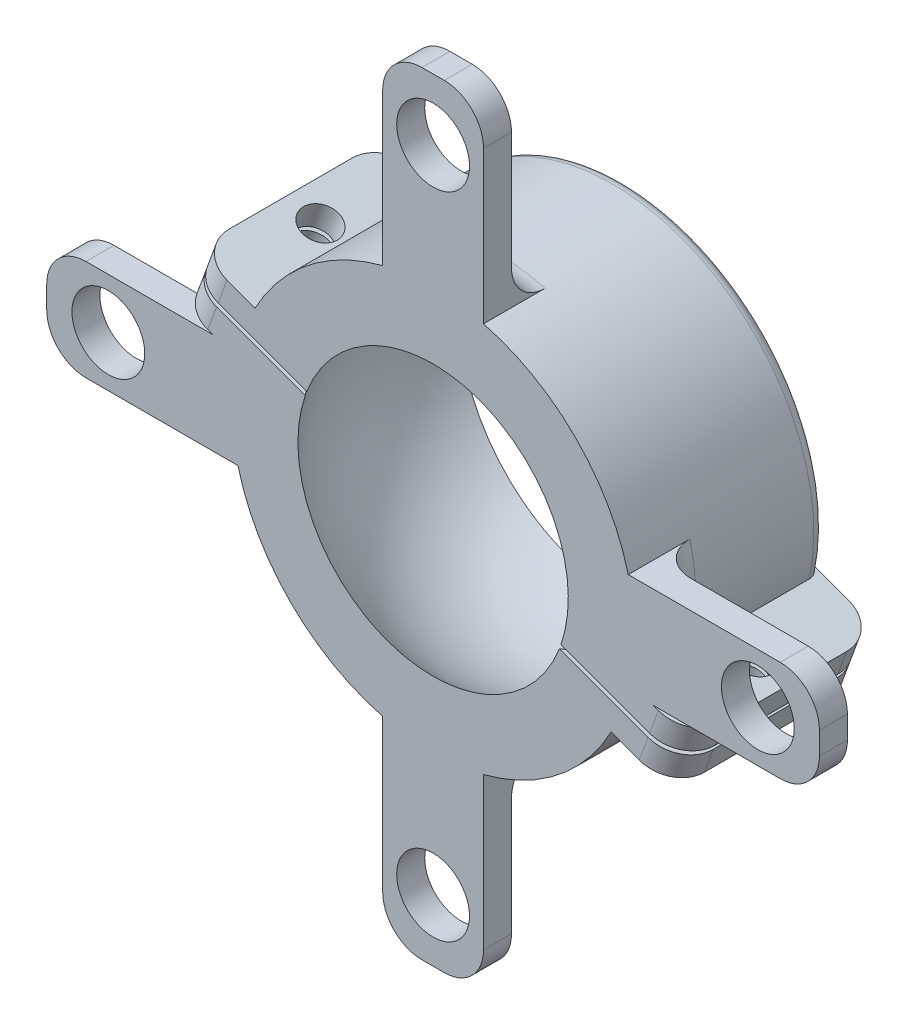
SolidWorks part; units mm, degrees
ref_plane "前视基准面" through (0, 0, 0) normal (0, 0, 1) x (1, 0, 0)
ref_plane "上视基准面" through (0, 0, 0) normal (0, 1, 0) x (1, 0, 0)
ref_plane "右视基准面" through (0, 0, 0) normal (1, 0, 0) x (0, 0, -1)
sketch "草图1" plane through (0, 0, 0) normal (0, 0, 1) x (1, 0, 0)
  circle A0 centre (0, 0) radius 18
extrude "凸台-拉伸1" add sketch "草图1" along normal blind 12.5 and the other way blind 6.5
sketch "草图2" plane through (0, 0, 0) normal (0, 0, 1) x (1, 0, 0)
  line L0 (0, 16) -> (0, -16)
  arc A0 (0, -16) -> (0, 16) centre (0, 0) ccw
revolve "切除-旋转1" cut sketch "草图2" angle 360 about L0
ref_plane "基准面1" through (17, 0, 0) normal (1, 0, 0) x (0, 0, -1)
ref_plane "基准面2" through (-17, 0, 0) normal (-1, 0, 0) x (0, 0, 1)
ref_plane "基准面3" through (0, 17, 0) normal (0, 1, 0) x (1, 0, 0)
ref_plane "基准面4" through (0, -17, 0) normal (0, -1, 0) x (-1, 0, 0)
sketch "草图4" plane through (17, 0, 0) normal (1, 0, 0) x (0, 0, -1)
  line L0 (-12.5, 18) -> (-12.5, -18) construction
  line L1 (-14.5, -4.5) -> (-10.5, -4.5)
  line L2 (-14.5, -4.5) -> (-14.5, 4.5)
  line L3 (-14.5, 4.5) -> (-10.5, 4.5)
  line L4 (-10.5, -4.5) -> (-10.5, 4.5)
  line L5 (-14.5, -4.5) -> (-10.5, 4.5) construction
  line L6 (-14.5, 4.5) -> (-10.5, -4.5) construction
  line L8 (-12.5, -4.5) -> (-10.5, -4.5)
  line L9 (-12.5, -4.5) -> (-12.5, 4.5)
  line L10 (-12.5, 4.5) -> (-10.5, 4.5)
  line L11 (-10.5, -4.5) -> (-10.5, 4.5)
  point P0 (-12.5, 0)
  dimension "D1" = 9
  dimension "D2" = 4
sketch "草图5" plane through (17, 0, 0) normal (1, 0, 0) x (0, 0, -1)
  line L1 (-10.5, 4.5) -> (-12.5, 4.5)
  line L2 (-10.5, 4.5) -> (-10.5, -4.5)
  line L3 (-10.5, -4.5) -> (-12.5, -4.5)
  line L4 (-12.5, 4.5) -> (-12.5, -4.5)
extrude "凸台-拉伸2" add sketch "草图5" along normal blind 17.5 and the other way blind 1
sketch "草图6" plane through (-17, 0, 0) normal (-1, 0, 0) x (0, 0, 1)
  line L1 (12.5, 4.5) -> (10.5, 4.5)
  line L2 (12.5, 4.5) -> (12.5, -4.5)
  line L3 (12.5, -4.5) -> (10.5, -4.5)
  line L4 (10.5, 4.5) -> (10.5, -4.5)
extrude "凸台-拉伸3" add sketch "草图6" along normal blind 17.5 and the other way blind 1
sketch "草图7" plane through (0, 17, 0) normal (0, 1, 0) x (1, 0, 0)
  line L0 (-17.4284, -12.5) -> (17.4284, -12.5) construction
  line L1 (-4.5, -14.5) -> (4.5, -14.5)
  line L2 (-4.5, -14.5) -> (-4.5, -10.5)
  line L3 (-4.5, -10.5) -> (4.5, -10.5)
  line L4 (4.5, -14.5) -> (4.5, -10.5)
  line L5 (-4.5, -14.5) -> (4.5, -10.5) construction
  line L6 (-4.5, -10.5) -> (4.5, -14.5) construction
  point P0 (0, -12.5)
  dimension "D1" = 4
  dimension "D2" = 9
sketch "草图8" plane through (0, 17, 0) normal (0, 1, 0) x (1, 0, 0)
  line L0 (-4.5, -14.5) -> (-4.5, -10.5) construction
  line L1 (4.5, -10.5) -> (-4.5, -10.5)
  line L2 (4.5, -10.5) -> (4.5, -12.5)
  line L3 (4.5, -12.5) -> (-4.5, -12.5)
  line L4 (-4.5, -10.5) -> (-4.5, -12.5)
extrude "凸台-拉伸4" add sketch "草图8" along normal blind 17.5 and the other way blind 1
sketch "草图9" plane through (0, -17, 0) normal (0, -1, 0) x (-1, 0, 0)
  line L1 (-4.5, -12.5) -> (4.5, -12.5)
  line L2 (-4.5, -12.5) -> (-4.5, -10.5)
  line L3 (-4.5, -10.5) -> (4.5, -10.5)
  line L4 (4.5, -12.5) -> (4.5, -10.5)
extrude "凸台-拉伸5" add sketch "草图9" along normal blind 17.5 and the other way blind 1
ref_axis "基准轴1" through (0, 0, -6.5) along (0, 0, 1)
ref_plane "基准面6" through (0, 0, 0) normal (0.342, 0.9397, 0) x (0, 0, 1)
ref_plane "基准面7" through (0, 0, 0) normal (-0.9397, 0.342, 0) x (0, 0, 1)
ref_plane "基准面8" through (-15.9748, 5.8143, 0) normal (-0.9397, 0.342, 0) x (0, 0, 1)
ref_plane "基准面9" through (15.9748, -5.8143, 0) normal (0.9397, -0.342, 0) x (0, 0, -1)
sketch "草图12" plane through (-15.9748, 5.8143, 0) normal (-0.9397, 0.342, 0) x (0, 0, 1)
  line L0 (12.5, -1.7323) -> (12.5, 14.8383) construction
  line L1 (-12.5, -2.5) -> (12.5, -2.5)
  line L2 (-12.5, -2.5) -> (-12.5, 2.5)
  line L3 (-12.5, 2.5) -> (12.5, 2.5)
  line L4 (12.5, -2.5) -> (12.5, 2.5)
  line L5 (-12.5, -2.5) -> (12.5, 2.5) construction
  line L6 (-12.5, 2.5) -> (12.5, -2.5) construction
  line L7 (12.5, -2.5) -> (-6.5, -2.5)
  point P0 (0, 0)
  dimension "D1" = 5
sketch "草图14" plane through (-15.9748, 5.8143, 0) normal (-0.9397, 0.342, 0) x (0, 0, 1)
  line L1 (-6.5, -2.5) -> (12.5, -2.5)
  line L2 (-6.5, -2.5) -> (-6.5, 2.5)
  line L3 (-6.5, 2.5) -> (12.5, 2.5)
  line L4 (12.5, -2.5) -> (12.5, 2.5)
extrude "凸台-拉伸6" add sketch "草图14" along normal blind 6.5
sketch "草图15" plane through (15.9748, -5.8143, 0) normal (0.9397, -0.342, 0) x (0, 0, -1)
  line L1 (-12.5, -2.5) -> (6.5, -2.5)
  line L2 (-12.5, -2.5) -> (-12.5, 2.5)
  line L3 (-12.5, 2.5) -> (6.5, 2.5)
  line L4 (6.5, -2.5) -> (6.5, 2.5)
extrude "凸台-拉伸7" add sketch "草图15" along normal blind 6.5
sketch "草图16" plane through (22.0828, -8.0375, 0) normal (0.9397, -0.342, 0) x (0, 0, -1)
  line L0 (-12.5, 2.5) -> (-12.5, 0.5)
  line L1 (-12.5, 2.5) -> (-12.5, -2.5) construction
  line L2 (6.5, -2.5) -> (6.5, -0.5)
  line L3 (6.5, -2.5) -> (6.5, 2.5) construction
  line L5 (-12.5, 0.5) -> (6.5, 0.5)
  line L6 (-12.5, 0.5) -> (-12.5, -0.5)
  line L7 (-12.5, -0.5) -> (6.5, -0.5)
  line L8 (6.5, 0.5) -> (6.5, -0.5)
  dimension "D1" = 1
sketch "草图17" plane through (22.0828, -8.0375, 0) normal (0.9397, -0.342, 0) x (0, 0, -1)
  line L0 (-12.5, 0.5) -> (-12.5, 0.2)
  line L5 (6.5, -0.5) -> (6.5, -0.2)
  line L7 (6.5, -0.2) -> (-12.5, -0.2)
  line L8 (6.5, -0.2) -> (6.5, 0.2)
  line L9 (6.5, 0.2) -> (-12.5, 0.2)
  line L10 (-12.5, -0.2) -> (-12.5, 0.2)
  line L11 (-12.5, 0.2) -> (6.5, 0.2)
  line L12 (-12.5, 0.2) -> (-12.5, -0.2)
  line L13 (-12.5, -0.2) -> (6.5, -0.2)
  line L14 (6.5, 0.2) -> (6.5, -0.2)
  line M5 (-12.5, 2.5) -> (-12.5, -2.5)
  line M7 (6.5, -2.5) -> (6.5, 2.5)
ref_plane "基准面10" through (0, 0, 12.5) normal (0, 0, 1) x (1, 0, 0)
sketch "草图26" plane through (0, 0, 12.5) normal (0, 0, 1) x (1, 0, 0)
  line L0 (0, 35) -> (0, 29)
  line L1 (4.5, 34.5) -> (-4.5, 34.5)
  line L2 (-34.5, 4.5) -> (-34.5, -4.5)
  line L3 (-35, 0) -> (-29, 0)
  line L4 (-4.5, -34.5) -> (4.5, -34.5)
  line L5 (0, -35) -> (0, -29)
  line L6 (34.5, 4.5) -> (34.5, -4.5)
  line L7 (35, 0) -> (29, 0)
  circle A0 centre (0, 0) radius 35
  circle A1 centre (0, 29) radius 2.7
  circle A2 centre (-29, 0) radius 2.7
  circle A3 centre (0, -29) radius 2.7
  circle A4 centre (29, 0) radius 2.7
sketch "草图27" plane through (0, 0, 12.5) normal (0, 0, 1) x (1, 0, 0)
  circle A0 centre (0, 29) radius 3.05
  circle A1 centre (-29, 0) radius 3.05
  circle A2 centre (29, 0) radius 3.05
  circle A3 centre (0, -29) radius 3.05
extrude "切除-拉伸1" cut sketch "草图17" against normal blind 50 contours L9 L7 M7 M5 region at (22.0828, -8.0375, 3)
sketch "草图34" plane through (0, 0, 12.5) normal (0, 0, 1) x (1, 0, 0)
  circle A0 centre (29, 0) radius 3.05
  circle A1 centre (0, -29) radius 3.05
  circle A2 centre (0, 29) radius 3.05
  circle A3 centre (-29, 0) radius 3.05
extrude "切除-拉伸3" cut sketch "草图34" against normal blind 2
sketch "草图35" plane through (0, 0, 10.5) normal (0, 0, -1) x (-1, 0, 0)
  line L0 (-4.5, -17) -> (4.5, -17) construction
  line L1 (-4.5, -34.5) -> (4.5, -34.5)
  line L2 (-4.5, -34.5) -> (-4.5, -17)
  line L3 (-4.5, -17) -> (4.5, -17)
  line L4 (4.5, -34.5) -> (4.5, -17)
  line L5 (17.4284, -4.5) -> (17, -4.5)
  line L6 (17, -14.85) -> (17, 14.85) construction
  line L7 (4.5, 17) -> (-4.5, 17) construction
  line L8 (17, -4.5) -> (34.5, -4.5)
  line L9 (17, -4.5) -> (17, 4.5)
  line L10 (17, 4.5) -> (34.5, 4.5)
  line L11 (34.5, -4.5) -> (34.5, 4.5)
  line L12 (-4.5, 34.5) -> (4.5, 34.5)
  line L13 (-4.5, 34.5) -> (-4.5, 17)
  line L14 (-4.5, 17) -> (4.5, 17)
  line L15 (4.5, 34.5) -> (4.5, 17)
  line L16 (14.85, 17) -> (-14.85, 17) construction
  line L17 (-17, 4.5) -> (-17, -4.5) construction
  line L18 (-34.5, -4.5) -> (-17, -4.5)
  line L19 (-34.5, -4.5) -> (-34.5, 4.5)
  line L20 (-34.5, 4.5) -> (-17, 4.5)
  line L21 (-17, -4.5) -> (-17, 4.5)
  circle A0 centre (0, 29) radius 3.05
  circle A1 centre (29, 0) radius 3.05
  circle A2 centre (-29, 0) radius 3.05
  circle A3 centre (0, -29) radius 3.05
  circle M1 centre (0, -29) radius 3.05
  line M2 (4.5, -34.5) -> (4.5, -17.4284)
  arc M3 (4.5, -17.4284) -> (-4.5, -17.4284) centre (0, 0) cw
  line M4 (-4.5, -17.4284) -> (-4.5, -34.5)
  line M5 (-4.5, -34.5) -> (4.5, -34.5)
extrude "凸台-拉伸8" add sketch "草图35" along normal blind 2.5 contours L18 L21 L20 L19 A2 | L8 L11 L10 L9 L5 A1 | M5 M2 M3 M4 M1 | L15 L12 L13 L14 A0 region at (0, -25.4671, 10.5) region at (-25.0096, 0, 10.5) region at (0, 25.0096, 10.5) region at (25.0096, 0, 10.5)
sketch "草图36" plane through (0, 0, 12.5) normal (0, 0, 1) x (1, 0, 0)
  circle A0 centre (0, 0) radius 35
extrude "切除-拉伸4" cut sketch "草图36" against normal blind 2
sketch "草图37" plane through (-0.8551, -2.3492, 0) normal (-0.342, -0.9397, 0) x (0.9397, -0.342, 0)
  line L0 (20.6628, 10.5) -> (20.6628, -6.5)
  line L1 (17.8255, 10.5) -> (23.5, 10.5) construction
  line L2 (23.5, -6.5) -> (17.8255, -6.5) construction
  circle A0 centre (20.6628, 2) radius 1.6
extrude "切除-拉伸5" cut sketch "草图37" against normal blind 8 contours L0 A0 | L0 A0 region at (19.1997, -9.6486, 2) region at (17.9235, -9.1841, 2)
sketch "草图39" plane through (0.8551, 2.3492, 0) normal (0.342, 0.9397, 0) x (0.9397, -0.342, 0)
  line L0 (-20.6628, 6.5) -> (-20.6628, -10.5)
  line L1 (-23.5, 6.5) -> (-17.8255, 6.5) construction
  line L2 (-17.8255, -10.5) -> (-23.5, -10.5) construction
  circle A0 centre (-20.6628, -2) radius 1.6
extrude "切除-拉伸6" cut sketch "草图39" against normal blind 8 contours L0 A0 | L0 A0 region at (-17.9235, 9.1841, 2) region at (-19.1997, 9.6486, 2)
fillet "圆角1" radius 3 4 edges at (-22.5445, 6.7689, 10.5) (-22.5445, 6.7689, -6.5) (21.621, -9.3061, 10.5) (21.621, -9.3061, -6.5)
fillet "圆角2" radius 3.5 4 edges at (-34.5, 4.5, 9.25) (-34.5, -4.5, 9.25) (-4.5, -34.5, 9.25) (4.5, -34.5, 9.25)
fillet "圆角3" radius 3.5 4 edges at (34.5, -4.5, 9.25) (34.5, 4.5, 9.25) (4.5, 34.5, 9.25) (-4.5, 34.5, 9.25)
sketch "草图40" plane through (0, 0, 8) normal (0, 0, -1) x (-1, 0, 0)
  circle A0 centre (0, 29) radius 3.25
  circle A1 centre (29, 0) radius 3.25
  circle A2 centre (-29, 0) radius 3.25
  circle A3 centre (0, -29) radius 3.25
extrude "切除-拉伸7" cut sketch "草图40" against normal blind 8 contours A2 | A0 | A1 | A3
fillet "圆角4" radius 3 2 edges at (0, 18, 8) (17.9958, 0.3866, 8)
fillet "圆角5" radius 3 2 edges at (0, -18, 8) (-17.9958, -0.3866, 8)
fillet "圆角6" radius 3 4 edges at (22.5445, -6.7689, -6.5) (22.5445, -6.7689, 10.5) (-21.621, 9.3061, 10.5) (-21.621, 9.3061, -6.5)
fillet "圆角7" radius 1 1 edges at (6.1564, 16.9145, -6.5)
fillet "圆角8" radius 1 1 edges at (-6.1564, -16.9145, -6.5)
